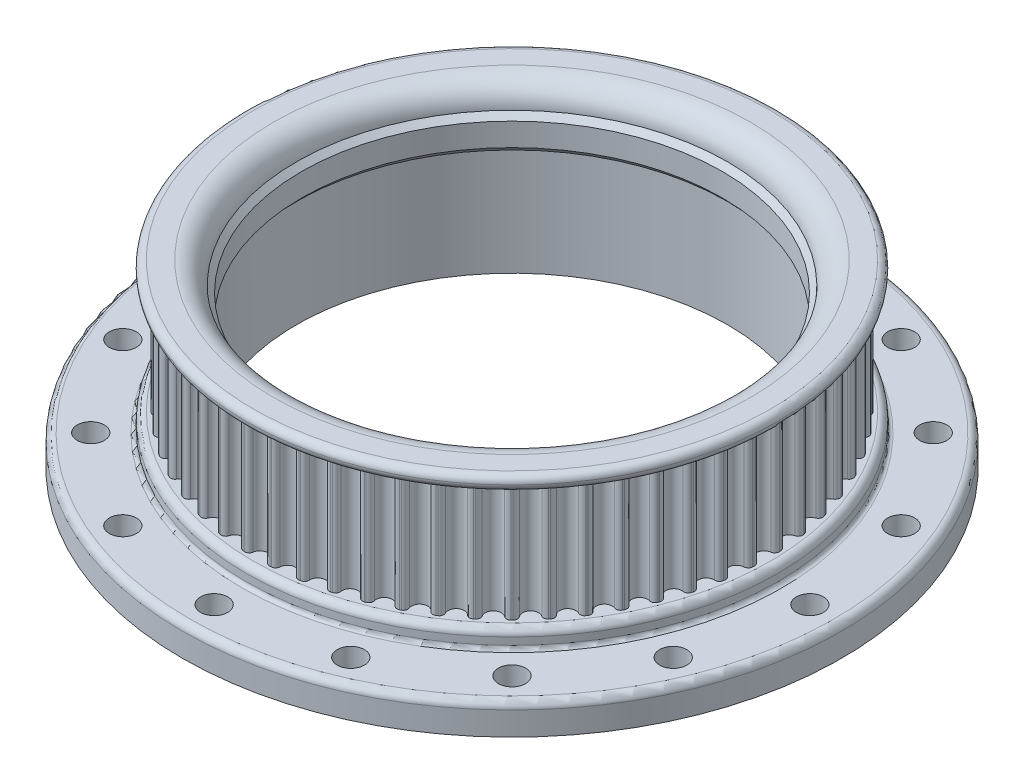
SolidWorks part; units mm, degrees
ref_plane "Front Plane" through (0, 0, 0) normal (0, 0, 1) x (1, 0, 0)
ref_plane "Top Plane" through (0, 0, 0) normal (0, 1, 0) x (1, 0, 0)
ref_plane "Right Plane" through (0, 0, 0) normal (1, 0, 0) x (0, 0, -1)
sketch "Sketch1" plane through (0, 0, 0) normal (0, 1, 0) x (1, 0, 0)
  line L0 (0, 0) -> (0, 28.2667) construction
  line L1 (0, 0) -> (2.9202, 27.7837) construction
  circle A0 centre (0, 0) radius 28.2667 construction
  circle A1 centre (0, 0) radius 27.0467 construction
  circle A2 centre (0, 27.9367) radius 0.89 construction
  circle A5 centre (2.9202, 27.7837) radius 0.89 construction
  arc A6 (0, 27.0467) -> (0.8804, 27.8061) centre (0, 27.9367) ccw
  arc A7 (0.8804, 27.8061) -> (1.3997, 28.2321) centre (1.3749, 27.7327) cw
  arc A8 (1.559, 28.2237) -> (2.031, 27.7458) centre (1.5314, 27.7245) cw
  arc A9 (2.8272, 26.8986) -> (2.031, 27.7458) centre (2.9202, 27.7837) cw
  arc A10 (1.3997, 28.2321) -> (1.559, 28.2237) centre (0, 0) cw
  arc A11 (0, 27.0467) -> (2.8272, 26.8986) centre (0, 0) ccw
  dimension "D1" = 56.5335
  dimension "D3" = 1.78
  dimension "D4" = 0.5
  dimension "D2" = 1.22
  dimension "D5" = 6
extrude "Boss-Extrude1" add sketch "Sketch1" along normal mid plane 13 contours A6 A11 A9 A8 A7 region at (0.001, 0, -0.0192)
ref_axis "Axis1" through (0, 3.3, 0) along (0, -1, 0)
pattern_circular "CirPattern1" count 60 over 360 about axis through (0, 3.3, 0) along (0, -1, 0) of "Boss-Extrude1"
sketch "Sketch2" plane through (0, 0, 0) normal (1, 0, 0) x (0, 0, -1)
  line L10 (0, 6.5) -> (29.4415, 6.5) construction
  line L11 (0, 6.5) -> (0, 8.0875) construction
  line L12 (0, 8.0875) -> (29.4415, 8.0875) construction
  line L15 (29.4415, 6.5) -> (29.4415, 8.0875) construction
  line L20 (0, 3.3) -> (0, -3.3) construction
  line L22 (29.4415, 8.0875) -> (0, 8.0875)
  line L23 (29.4415, 8.0875) -> (29.4415, 6.5)
  line L24 (29.4415, 6.5) -> (0, 6.5)
  line L25 (0, 8.0875) -> (0, 6.5)
  dimension "D1" = 1.5875
  dimension "D2" = 29.4415
  dimension "D3" = 6.5
revolve "Revolve3" add sketch "Sketch2" angle 360 about axis through (0, 3.3, 0) along (0, -1, 0) region at (0, 7.2937, -14.7207)
mirror "Mirror1" about plane through (0, 0, 0) normal (0, 1, 0) of "Revolve3"
sketch "Sketch3" plane through (0, 0, 0) normal (0, -1, 0) x (-1, 0, 0)
  circle A0 centre (0, 0) radius 23.8852
  dimension "D1" = 47.7705
extrude "Cut-Extrude1" cut sketch "Sketch3" against normal through all both and the other way through all
sketch "Sketch5" plane through (0, 0, 0) normal (0, 0, 1) x (1, 0, 0)
  line L0 (29.4415, -6.5) -> (-29.4415, -6.5) construction
  line L1 (-29.854, -8.5) -> (-36.5125, -8.5)
  line L2 (-36.5125, -8.5) -> (-36.5125, -10.0875)
  line L3 (-36.5125, -10.0875) -> (-23.8852, -10.0875)
  line L4 (-23.8852, -10.0875) -> (-23.8852, -8.0875)
  line L5 (-29.4415, -8.0875) -> (29.4415, -8.0875) construction
  line L6 (-23.8852, -8.0875) -> (-29.4415, -8.0875)
  arc A0 (-29.4415, -8.0875) -> (-29.854, -8.5) centre (-29.854, -8.0875) cw
  dimension "D1" = 2
  dimension "D2" = 36.5125
  dimension "D3" = 1.5875
revolve "Revolve4" add sketch "Sketch5" angle 360 about axis through (0, 3.3, 0) along (0, -1, 0)
sketch "Sketch6" plane through (0, -8.5, 0) normal (0, 1, 0) x (1, 0, 0)
  line L0 (-30.488, 12.6286) -> (0, 0) construction
  line L1 (0, 0) -> (-36.5125, 0) construction
  circle A0 centre (-30.488, 12.6286) radius 1.5
  circle A1 centre (0, 0) radius 36.5125 construction
  dimension "D2" = 3
  dimension "D1" = 33
  dimension "D3" = 22.5
extrude "Cut-Extrude2" cut sketch "Sketch6" against normal through all
pattern_circular "CirPattern2" count 16 over 360 about axis through (0, 3.3, 0) along (0, -1, 0) of "Cut-Extrude2"
fillet "Fillet1" radius 2.54 1 edges at (0, 8.0875, -23.8852)
sketch "Sketch9" plane through (0, -10.0875, 0) normal (0, -1, 0) x (1, 0, 0)
  circle A1 centre (0, 0) radius 36.5125
  circle A2 centre (0, 0) radius 29
  circle A3 centre (-30.488, -12.6286) radius 1.5
  circle A4 centre (-30.488, -12.6286) radius 1.5
  circle A5 centre (-23.3345, -23.3345) radius 1.5
  circle A6 centre (-23.3345, -23.3345) radius 1.5
  circle A7 centre (23.3345, 23.3345) radius 1.5
  circle A8 centre (23.3345, 23.3345) radius 1.5
  circle A9 centre (12.6286, 30.488) radius 1.5
  circle A10 centre (12.6286, 30.488) radius 1.5
  circle A11 centre (0, 33) radius 1.5
  circle A12 centre (0, 33) radius 1.5
  circle A13 centre (-12.6286, 30.488) radius 1.5
  circle A14 centre (-12.6286, 30.488) radius 1.5
  circle A15 centre (-23.3345, 23.3345) radius 1.5
  circle A16 centre (-23.3345, 23.3345) radius 1.5
  circle A17 centre (-30.488, 12.6286) radius 1.5
  circle A18 centre (-30.488, 12.6286) radius 1.5
  circle A19 centre (-33, 0) radius 1.5
  circle A20 centre (-33, 0) radius 1.5
  circle A21 centre (30.488, 12.6286) radius 1.5
  circle A22 centre (30.488, 12.6286) radius 1.5
  circle A23 centre (33, 0) radius 1.5
  circle A24 centre (33, 0) radius 1.5
  circle A25 centre (30.488, -12.6286) radius 1.5
  circle A26 centre (30.488, -12.6286) radius 1.5
  circle A27 centre (23.3345, -23.3345) radius 1.5
  circle A28 centre (23.3345, -23.3345) radius 1.5
  circle A29 centre (12.6286, -30.488) radius 1.5
  circle A30 centre (12.6286, -30.488) radius 1.5
  circle A31 centre (0, -33) radius 1.5
  circle A32 centre (0, -33) radius 1.5
  circle A33 centre (-12.6286, -30.488) radius 1.5
  circle A34 centre (-12.6286, -30.488) radius 1.5
  circle A35 centre (0, 0) radius 36.5125
  dimension "D18" = 58
  dimension "D2" = 0
  dimension "D3" = 0
  dimension "D4" = 0
  dimension "D5" = 0
  dimension "D6" = 0
  dimension "D7" = 0
  dimension "D8" = 0
  dimension "D9" = 0
  dimension "D10" = 0
  dimension "D11" = 0
  dimension "D12" = 0
  dimension "D13" = 0
  dimension "D14" = 0
  dimension "D15" = 0
  dimension "D16" = 0
  dimension "D17" = 0
  dimension "D19" = 0
extrude "Boss-Extrude2" add sketch "Sketch9" along normal up to surface (1.8125 mm away)
fillet "Fillet2" radius 0.7937 4 edges at (0, -6.5, 29.4415) (0, 6.5, 29.4415) (0, 8.0875, 29.4415) (0, -8.5, 36.5125)
sketch "Sketch10" plane through (0, 0, 0) normal (1, 0, 0) x (0, 0, -1)
  line L0 (-23.8852, 5.5475) -> (-23.8852, -10.0875)
  line L1 (23.8852, -10.0875) -> (23.8852, 5.5475)
  line L2 (23.8852, -10.0875) -> (23.8852, 5.5475)
  line L3 (-23.8852, 5.5475) -> (-23.8852, -10.0875)
  line L4 (-23.8852, 5.5475) -> (-23.307, 4.9125)
  line L5 (-23.307, 4.9125) -> (-23.307, 2.3725)
  line L6 (-23.307, 2.3725) -> (-23.8852, 1.7375)
  line L7 (0, -24.8248) -> (0, 26.9181) construction
  line L8 (-23.8852, 5.5475) -> (-23.8852, 1.7375)
  dimension "D1" = 46.6141
  dimension "D2" = 2.54
  dimension "D3" = 3.81
revolve "Revolve5" add sketch "Sketch10" angle 360 about L7 region at (0, 3.6425, 23.6154)
equation "\"TEETH_NUM\"= 60"
equation "\"TOOTH_PITCH\"= 3mm"
equation "\"PITCH_LINE_OFFSET\"= .015in"
equation "\"DIAMETER_PER_GROOVE\"= \"OUTSIDE_DIAMETER\" / \"TEETH_NUM\" * 1in"
equation "\"PITCH_DIAMETER\"= ( ( \"TEETH_NUM\" * 3 - 1.31 ) / 3.1415 + .415 ) * 1mm"
equation "\"OUTSIDE_DIAMETER\"= \"PITCH_DIAMETER\" - \"PITCH_LINE_OFFSET\" * 2"
equation "\"D1@Sketch1\"=\"OUTSIDE_DIAMETER\""
equation "\"TOOTH_HEIGHT\"= 1.22mm"
equation "\"D2@Sketch1\"=\"TOOTH_HEIGHT\""
equation "\"TOOTH_DIAMETER\"= 1.78mm"
equation "\"INTERNAL_RADIUS\"= .5mm"
equation "\"D3@Sketch1\"=\"TOOTH_DIAMETER\""
equation "\"D5@Sketch1\"=360 / \"TEETH_NUM\""
equation "\"D4@Sketch1\"=\"INTERNAL_RADIUS\""
equation "\"D1@CirPattern1\"=\"TEETH_NUM\""
equation "\"BELT_GAP\"= 13mm"
equation "\"D2@Sketch2\"=\"PITCH_DIAMETER\"/2+1/32"
equation "\"D3@Sketch2\"=\"BELT_GAP\"/2"
equation "\"D1@Sketch3\"=\"PITCH_DIAMETER\"-.375"
equation "\"D1@Boss-Extrude1\"=\"BELT_GAP\""
equation "\"center_offset\"=0.75"
equation "\"Bearing_Diameter\"= 58mm"
equation "\"bolt_on_feature\"=16"
equation "\"D1@CirPattern2\"=\"bolt_on_feature\""
equation "\"D1@Sketch10\"=1.8342in + 0.001"
